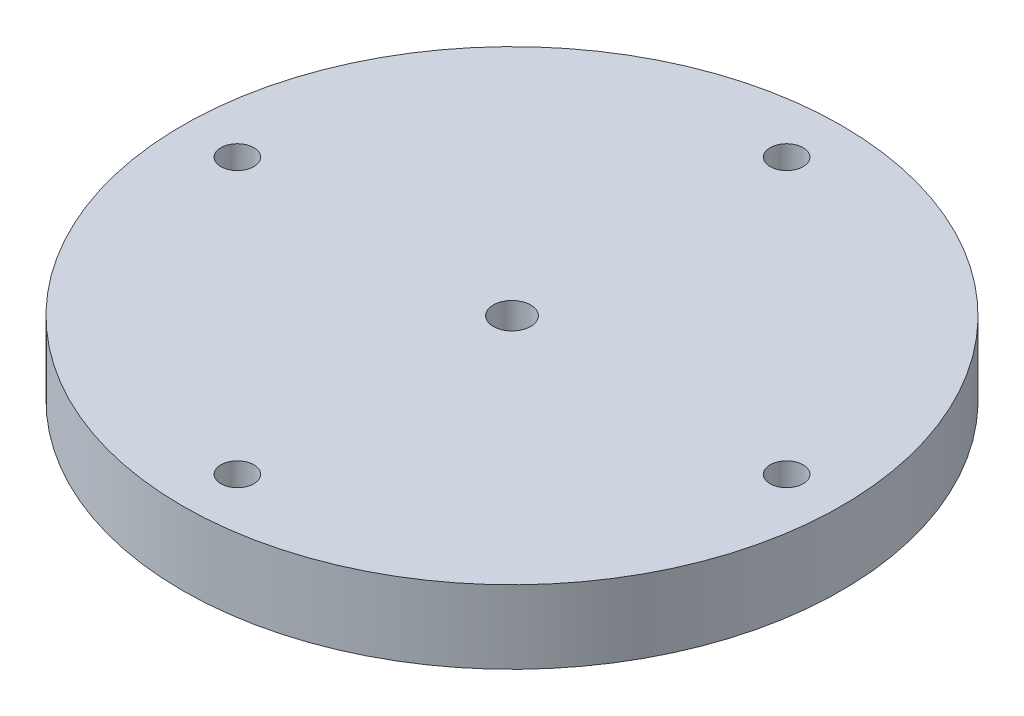
SolidWorks part; units mm, degrees
ref_plane "Front Plane" through (0, 0, 0) normal (0, 0, 1) x (1, 0, 0)
ref_plane "Top Plane" through (0, 0, 0) normal (0, 1, 0) x (1, 0, 0)
ref_plane "Right Plane" through (0, 0, 0) normal (1, 0, 0) x (0, 0, -1)
sketch "Sketch1" plane through (0, 0, 0) normal (0, 1, 0) x (1, 0, 0)
  circle A0 centre (0, 0) radius 45
  dimension "D1" = 90
extrude "Boss-Extrude1" add sketch "Sketch1" along normal blind 10
sketch "Sketch2" plane through (0, 10, 0) normal (0, 1, 0) x (1, 0, 0)
  line L0 (-1000, 0) -> (49000, 0) construction
  line L1 (0, -1000) -> (0, 49000) construction
  circle A0 centre (0, 0) radius 37.5 construction
  circle A1 centre (0, 37.5) radius 2.25
  circle A2 centre (-37.5, 0) radius 2.25
  circle A3 centre (0, -37.5) radius 2.25
  circle A4 centre (37.5, 0) radius 2.25
  circle A5 centre (0, 0) radius 45 construction
  dimension "D1" = 7.5
  dimension "D2" = 4.5
  dimension "D3" = 4.5
  dimension "D4" = 4.5
  dimension "D5" = 4.5
extrude "Cut-Extrude1" cut sketch "Sketch2" against normal through all
sketch "Sketch3" plane through (0, 10, 0) normal (0, 1, 0) x (1, 0, 0)
  circle A0 centre (0, 0) radius 2.55
  dimension "D1" = 5.1
extrude "Cut-Extrude2" cut sketch "Sketch3" against normal through all
